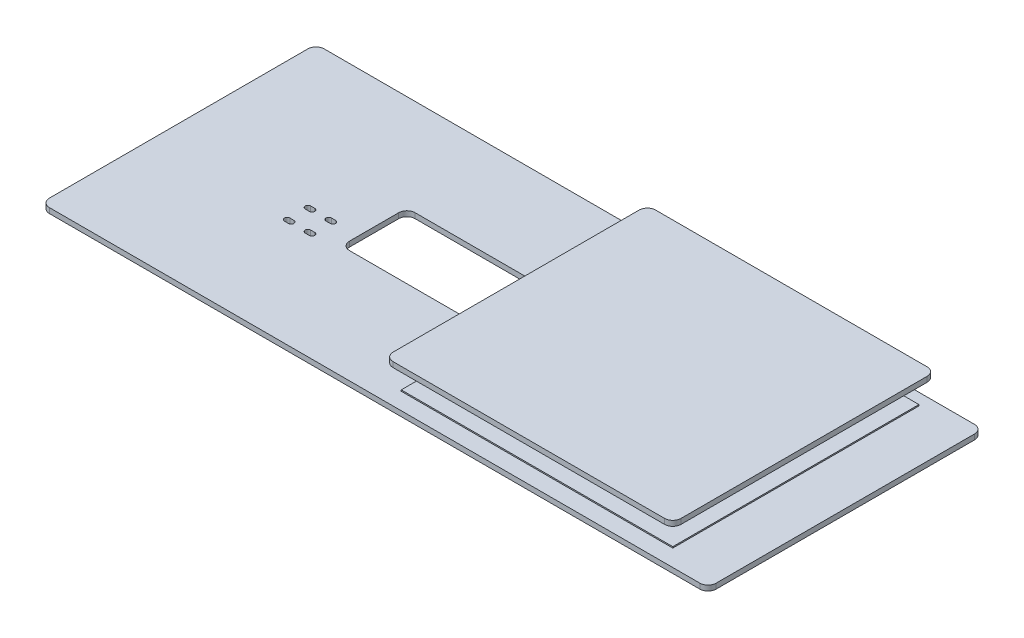
SolidWorks part; units mm, degrees
material "PC High Viscosity"
ref_plane "Front Plane" through (0, 0, 0) normal (0, 0, 1) x (1, 0, 0)
ref_plane "Top Plane" through (0, 0, 0) normal (0, 1, 0) x (1, 0, 0)
ref_plane "Right Plane" through (0, 0, 0) normal (1, 0, 0) x (0, 0, -1)
ref_axis "Axis1" through (0, -55, 0) along (0, 1, 0)
sketch "Sketch1" plane through (0, 0, 0) normal (0, 1, 0) x (1, 0, 0)
  line L1 (15, 150) -> (346, 150)
  line L2 (15, 150) -> (15, -150)
  line L3 (15, -150) -> (346, -150)
  line L4 (346, 150) -> (346, -150)
  line L5 (15, 150) -> (346, -150) construction
  line L6 (15, -150) -> (346, 150) construction
  point P0 (-102.8497, 0)
  point P10 (15, 0)
  dimension "D1" = 300
  dimension "D2" = 331
  dimension "D3" = 15
extrude "Boss-Extrude1" add sketch "Sketch1" along normal blind 1.53
sketch "Sketch2" plane through (0, 1.53, 0) normal (0, 1, 0) x (1, 0, 0)
  circle A0 centre (-118.3585, -98.6077) radius 5.6331
  circle A1 centre (-137.9382, 113.4036) radius 5.6331
  circle A2 centre (146.0786, 131.7762) radius 5.6331
  circle A3 centre (128.6901, -129.1506) radius 5.6331
ref_plane "Plane1" through (0, -3, 0) normal (0, 1, 0) x (1, 0, 0)
sketch "Sketch3" plane through (0, -3, 0) normal (0, 1, 0) x (1, 0, 0)
  line L1 (-406.4, 167.5) -> (406.4, 167.5)
  line L2 (-406.4, 167.5) -> (-406.4, -167.5)
  line L3 (-406.4, -167.5) -> (406.4, -167.5)
  line L4 (406.4, 167.5) -> (406.4, -167.5)
  line L5 (-406.4, 167.5) -> (406.4, -167.5) construction
  line L6 (-406.4, -167.5) -> (406.4, 167.5) construction
  point P0 (0, 0)
  dimension "D1" = 335
  dimension "D2" = 812.8
extrude "Boss-Extrude2" add sketch "Sketch3" against normal blind 6.35 separate body
sketch "Sketch4" plane through (0, -9.35, 0) normal (0, -1, 0) x (1, 0, 0)
  line L0 (-236.4105, 35.2529) -> (-211.0105, 35.2529) construction
  line L1 (-236.4105, 35.2529) -> (-236.4105, 9.8529) construction
  line L2 (-236.4105, 9.8529) -> (-211.0105, 9.8529) construction
  line L3 (-211.0105, 35.2529) -> (-211.0105, 9.8529) construction
  line L4 (-236.4105, 35.2529) -> (-211.0105, 9.8529) construction
  line L5 (-236.4105, 9.8529) -> (-211.0105, 35.2529) construction
  line L6 (-208.5105, 9.8529) -> (-213.5105, 9.8529) construction
  line L8 (199.23, 58.4877) -> (199.23, -13.382) construction
  line L11 (-208.5105, 6.5509) -> (-213.5105, 6.5509)
  line L12 (-208.5105, 13.1549) -> (-213.5105, 13.1549)
  line L13 (-233.9105, 9.8529) -> (-238.9105, 9.8529) construction
  line L14 (-233.9105, 6.5509) -> (-238.9105, 6.5509)
  line L15 (-233.9105, 13.1549) -> (-238.9105, 13.1549)
  line L16 (-208.5105, 35.2529) -> (-213.5105, 35.2529) construction
  line L17 (-208.5105, 31.9509) -> (-213.5105, 31.9509)
  line L18 (-208.5105, 38.5549) -> (-213.5105, 38.5549)
  line L19 (-233.9105, 35.2529) -> (-238.9105, 35.2529) construction
  line L20 (-233.9105, 31.9509) -> (-238.9105, 31.9509)
  line L21 (-233.9105, 38.5549) -> (-238.9105, 38.5549)
  circle A0 centre (-236.4105, 35.2529) radius 3.302 construction
  circle A1 centre (-236.4105, 9.8529) radius 3.302 construction
  circle A2 centre (-211.0105, 35.2529) radius 3.302 construction
  circle A3 centre (-211.0105, 9.8529) radius 3.302 construction
  arc A6 (-208.5105, 6.5509) -> (-208.5105, 13.1549) centre (-208.5105, 9.8529) ccw
  arc A7 (-213.5105, 13.1549) -> (-213.5105, 6.5509) centre (-213.5105, 9.8529) ccw
  arc A8 (-233.9105, 6.5509) -> (-233.9105, 13.1549) centre (-233.9105, 9.8529) ccw
  arc A9 (-238.9105, 13.1549) -> (-238.9105, 6.5509) centre (-238.9105, 9.8529) ccw
  arc A10 (-208.5105, 31.9509) -> (-208.5105, 38.5549) centre (-208.5105, 35.2529) ccw
  arc A11 (-213.5105, 38.5549) -> (-213.5105, 31.9509) centre (-213.5105, 35.2529) ccw
  arc A12 (-233.9105, 31.9509) -> (-233.9105, 38.5549) centre (-233.9105, 35.2529) ccw
  arc A13 (-238.9105, 38.5549) -> (-238.9105, 31.9509) centre (-238.9105, 35.2529) ccw
  point P0 (-223.7105, 22.5529)
  point P7 (-211.0105, 9.8529)
  point P9 (-211.0105, 22.5529)
  point P16 (199.23, 22.5529)
  point P17 (-236.4105, 22.5529)
  point P25 (-236.4105, 9.8529)
  point P31 (-211.0105, 35.2529)
  point P39 (-236.4105, 35.2529)
  dimension "D4" = 6.604
  dimension "D1" = 25.4
  dimension "D2" = 25.4
  dimension "D3" = 211.0105
  dimension "D5" = 5
extrude "Cut-Extrude1" cut sketch "Sketch4" against normal blind 6.35
ref_plane "Plane2" through (0, 0, 0) normal (-1, 0, 0) x (0, 0, 1)
mirror "Mirror1" about plane through (0, 0, 0) normal (-1, 0, 0) of "Cut-Extrude1"
fillet "Fillet1" radius 10 4 edges at (-406.4, -6.175, -167.5) (-406.4, -6.175, 167.5) (406.4, -6.175, 167.5) (406.4, -6.175, -167.5)
sketch "Sketch5" plane through (0, 0, 0) normal (0, 1, 0) x (1, 0, 0)
  line L8 (356, -160) -> (356, 160)
  line L9 (356, 160) -> (5, 160)
  line L10 (5, 160) -> (5, -160)
  line L11 (5, -160) -> (356, -160)
  line L12 (356, -160) -> (356, 160)
  line L13 (356, 160) -> (5, 160)
  line L14 (5, 160) -> (5, -160)
  line L15 (5, -160) -> (356, -160)
  dimension "D1" = 10
extrude "Boss-Extrude3" add sketch "Sketch5" along normal blind 6.35 from offset 30 separate body
fillet "Fillet2" radius 10 4 edges at (5, 33.175, -160) (5, 33.175, 160) (356, 33.175, 160) (356, 33.175, -160)
sketch "Sketch6" plane through (0, -9.35, 0) normal (0, -1, 0) x (1, 0, 0)
  line L1 (-0.2875, -49.9992) -> (-178.0875, -49.9992)
  line L2 (-0.2875, -49.9992) -> (-0.2875, 30.0008)
  line L3 (-0.2875, 30.0008) -> (-178.0875, 30.0008)
  line L4 (-178.0875, -49.9992) -> (-178.0875, 30.0008)
  dimension "D1" = 50
  dimension "D2" = 80
  dimension "D3" = 177.8
  dimension "D4" = 0.2875
extrude "Cut-Extrude2" cut sketch "Sketch6" against normal blind 6.35
fillet "Fillet3" radius 10 4 edges at (-0.2875, -6.175, 30.0008) (-0.2875, -6.175, -49.9992) (-178.0875, -6.175, 30.0008) (-178.0875, -6.175, -49.9992)
